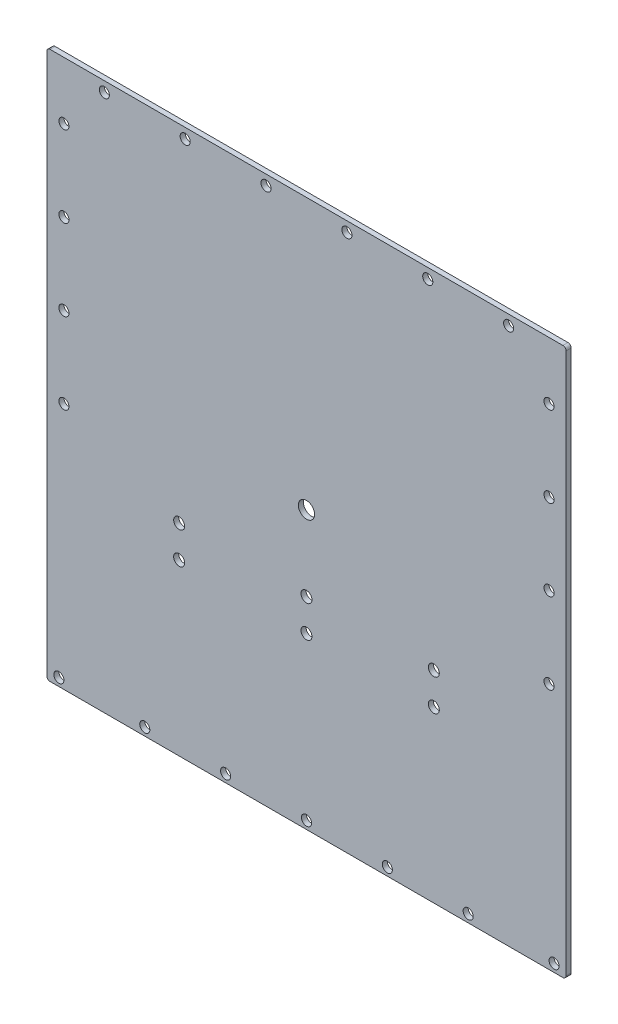
SolidWorks part; units mm, degrees
material "6061 Alloy"
ref_plane "Front Plane" through (0, 0, 0) normal (0, 0, 1) x (1, 0, 0)
ref_plane "Top Plane" through (0, 0, 0) normal (0, 1, 0) x (1, 0, 0)
ref_plane "Right Plane" through (0, 0, 0) normal (1, 0, 0) x (0, 0, -1)
sketch "Sketch2" plane through (0, 0, 0) normal (0, 0, 1) x (1, 0, 0)
  line L0 (0, -176.7623) -> (165.1, -176.7623)
  line L1 (0, 0) -> (165.1, 0)
  line L5 (82.55, 0) -> (82.55, -176.7623) construction
  line L6 (165.1, 0) -> (165.1, -176.7623)
  line L7 (0, 0) -> (0, -176.7623)
  line L8 (0, 0) -> (0, -176.7623)
  line L9 (0, -171.98) -> (165.1, -171.98)
  line L10 (1, 0) -> (1, -171.98)
  line L11 (164.1, -171.98) -> (164.1, 0)
  circle A31 centre (31.75, -169.48) radius 1.5875
  circle A32 centre (57.15, -169.48) radius 1.5875
  circle A33 centre (82.55, -169.48) radius 1.5875
  circle A34 centre (107.95, -169.48) radius 1.5875
  circle A35 centre (133.35, -169.48) radius 1.5875
  circle A63 centre (6.35, -18.05) radius 1.5875
  circle A65 centre (160.3375, -169.48) radius 1.5875
  circle A66 centre (4.7625, -169.48) radius 1.5875
  circle A67 centre (82.55, -85) radius 2.5527
  circle A69 centre (19.05, -3.175) radius 1.5875
  circle A70 centre (44.45, -3.175) radius 1.5875
  circle A71 centre (69.85, -3.175) radius 1.5875
  circle A72 centre (95.25, -3.175) radius 1.5875
  circle A73 centre (120.65, -3.175) radius 1.5875
  circle A74 centre (146.05, -3.175) radius 1.5875
  circle A76 centre (6.35, -43.45) radius 1.5875
  circle A77 centre (6.35, -68.85) radius 1.5875
  circle A78 centre (6.35, -94.25) radius 1.5875
  circle A81 centre (158.75, -68.85) radius 1.5875
  circle A82 centre (158.75, -94.25) radius 1.5875
  circle A83 centre (158.75, -43.45) radius 1.5875
  circle A84 centre (158.75, -18.05) radius 1.5875
  dimension "D9" = 3.175
  dimension "D4" = 3.175
  dimension "D21" = 5.1054
  dimension "D1" = 165.1
  dimension "D23" = 25.4
  dimension "D5" = 176.7623
  dimension "D8" = 31.75
  dimension "D11" = 7.2823
  dimension "D10" = 19.05
  dimension "D12" = 3.175
  dimension "D14" = 25.4
  dimension "D3" = 18.05
  dimension "D6" = 6.35
  dimension "D15" = 25.4
  dimension "D16" = 2.5
  dimension "D17" = 4.7625
  dimension "D18" = 1
  dimension "D19" = 1
  dimension "D20" = 85
  dimension "D22" = 5
  dimension "D13" = 3
  dimension "D7" = 4
extrude "Boss-Extrude2" add sketch "Sketch2" along normal blind 1.5875 contours L1 L0 A35 A34 A33 A32 A31 | L1 L5 A33 L0 L6 A35 A34 region at (3.3702, -85.99, 0)
fillet "Fillet1" radius 1 4 edges at (1, -171.98, 0.7937) (1, 0, 0.7937) (164.1, 0, 0.7937) (164.1, -171.98, 0.7937)
sketch "Sketch3" plane through (0, 0, 1.5875) normal (0, 0, 1) x (1, 0, 0)
  line L0 (2, -171.98) -> (163.1, -171.98) construction
  line L2 (1, -1) -> (1, -170.98) construction
  circle A0 centre (42.55, -108.6304) radius 1.725
  circle A1 centre (82.55, -108.6304) radius 1.725
  circle A2 centre (122.55, -108.6304) radius 1.725
  circle A3 centre (42.55, -118.6304) radius 1.725
  circle A4 centre (82.55, -118.6304) radius 1.725
  circle A5 centre (122.55, -118.6304) radius 1.725
  point P16 (0, 0)
  point P17 (0, 0)
  point P18 (0, 0)
  point P19 (0, 0)
  point P20 (0, 0)
  dimension "D4" = 3.45
  dimension "D1" = 40
  dimension "D2" = 40
  dimension "D3" = 63.3496
  dimension "D5" = 41.55
  dimension "D6" = 10
extrude "Cut-Extrude1" cut sketch "Sketch3" against normal through all both and the other way through all
equation "\"D19@Sketch2\"=\"D18@Sketch2\""
equation "\"D9@Sketch2\"=\"D4@Sketch2\""
